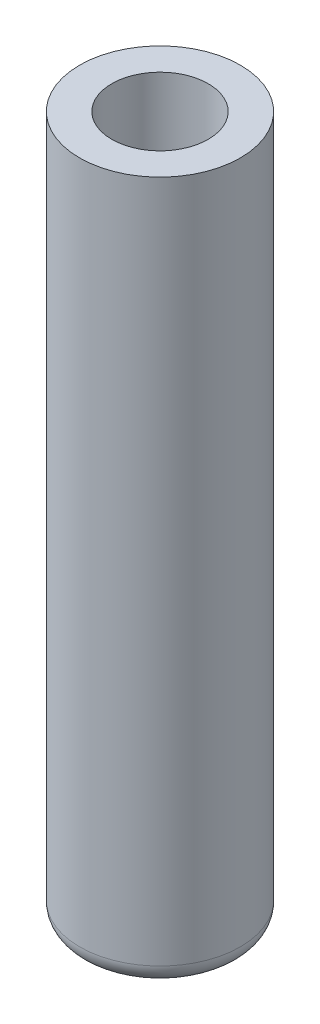
SolidWorks part; units mm, degrees
ref_plane "前视基准面" through (0, 0, 0) normal (0, 0, 1) x (1, 0, 0)
ref_plane "上视基准面" through (0, 0, 0) normal (0, 1, 0) x (1, 0, 0)
ref_plane "右视基准面" through (0, 0, 0) normal (1, 0, 0) x (0, 0, -1)
other "Configuration Table"
sketch "草图1" plane through (0, 0, 0) normal (0, 1, 0) x (1, 0, 0)
  circle A0 centre (0, 0) radius 2.4
  circle A1 centre (0, 0) radius 4
  dimension "D1" = 4.8
  dimension "D2" = 8
extrude "凸台-拉伸1" add sketch "草图1" along normal blind 35
fillet "圆角1" radius 1 1 edges at (0, 0, 4)
